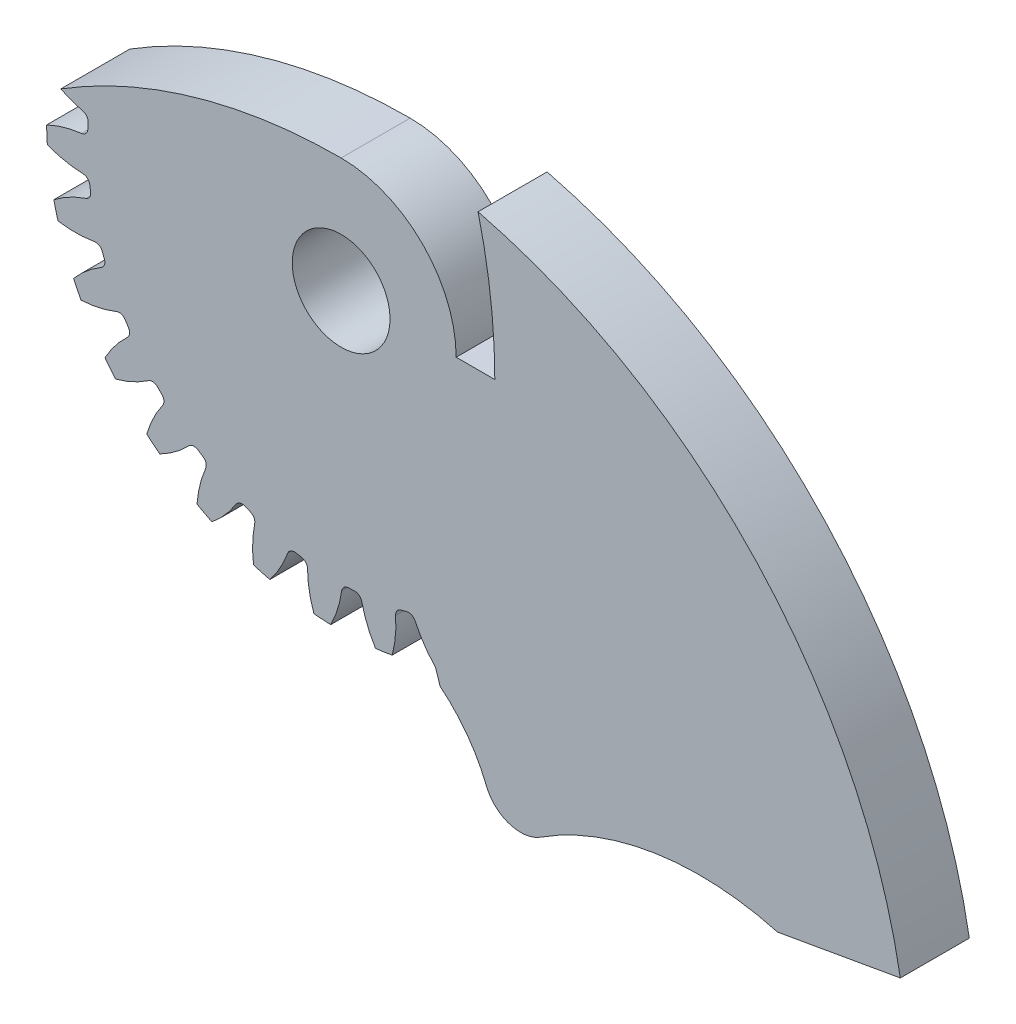
SolidWorks part; units mm, degrees
material "ABS"
ref_plane "Front" through (0, 0, 0) normal (0, 0, 1) x (1, 0, 0)
ref_plane "Top" through (0, 0, 0) normal (0, 1, 0) x (1, 0, 0)
ref_plane "Right" through (0, 0, 0) normal (1, 0, 0) x (0, 0, -1)
sketch "Sketch3" plane through (0, 0, 0) normal (0, 0, 1) x (1, 0, 0)
  circle A0 centre (0, 0) radius 40.64
  dimension "od" = 81.28
extrude "gearBody" add sketch "Sketch3" along normal blind 9.525
sketch "Sketch2" plane through (0, 0, 0) normal (0, 0, 1) x (1, 0, 0)
  line L0 (0, 0) -> (34.0786, 14.1158) construction
  line L1 (45.4751, -11.4855) -> (0, 0) construction
  line L2 (0, 0) -> (36.3143, 0) construction
  line L3 (38.0972, -0.458) -> (37.8451, -4.4001) construction
  line L5 (37.9712, -2.4291) -> (0, 0) construction
  line L7 (0, 0) -> (36.8864, 0) construction
  arc A0 (36.879, -0.7403) -> (36.6727, -3.9649) centre (0, 0) ccw construction
  arc A1 (40.637, 0.4947) -> (40.2427, -5.6687) centre (0, 0) ccw construction
  arc A2 (38.0972, -0.458) -> (37.8451, -4.4001) centre (0, 0) ccw construction
  arc A3 (34.9015, -2.6404) -> (34.9534, -1.8283) centre (0, 0) ccw
  arc A4 (45.4751, -11.4855) -> (35.6466, -3.6712) centre (32.0022, -18.3431) ccw
  arc A5 (45.4751, -11.4855) -> (46.5679, 5.5974) centre (0, 0) ccw
  arc A6 (46.5679, 5.5974) -> (35.8238, -0.9008) centre (34.0786, 14.1158) cw
  arc A7 (34.9534, -1.8283) -> (35.8238, -0.9008) centre (35.9376, -1.8798) cw
  arc A8 (35.6466, -3.6712) -> (34.9015, -2.6404) centre (35.8842, -2.7147) cw
  point P6 (46.5679, 5.5974)
  point P22 (45.4751, -11.4855)
  dimension "baseDia" = 73.7729
  dimension "od" = 81.28
  dimension "pd" = 76.2
  dimension "rd" = 70.0024
  dimension "rFillet" = 0.9855
  dimension "pointX" = 46.5679
  dimension "pointY" = 5.5974
  dimension "CTT" = 3.9421
  dimension "flankCenterAngle" = 22.5
extrude "toothCut" cut sketch "Sketch2" along normal through all
pattern_circular "CirPattern1" count 30 over 360 about axis through (0, 0, 9.525) along (0, 0, -1) of "toothCut"
sketch "hub1Dia" plane through (0, 0, 0) normal (0, 0, -1) x (-1, 0, 0)
  circle A0 centre (0, 0) radius 12.7
  dimension "hub1Dia" = 25.4
sketch "hub2Dia" plane through (0, 0, 9.525) normal (0, 0, 1) x (1, 0, 0)
  circle A0 centre (0, 0) radius 12.7
  dimension "hub2dia" = 25.4
sketch "boreDia" plane through (0, 0, 0) normal (0, 0, 1) x (1, 0, 0)
  circle A0 centre (0, 0) radius 6.7469
  dimension "boreDia" = 13.4937
extrude "bore" cut sketch "boreDia" against normal mid plane 25400
sketch "Sketch4" plane through (0, 0, 9.525) normal (0, 0, 1) x (1, 0, 0)
  circle A0 centre (0, -57.15) radius 78.359
  arc A2 (-42.9159, 8.4119) -> (42.9159, 8.4119) centre (0, 0) cw
  dimension "D1" = 156.718
  dimension "D2" = 57.15
extrude "Cut-Extrude1" cut sketch "Sketch4" against normal through all contours A0 region at (0, 27.8712, 9.525)
sketch "Sketch5" plane through (0, 0, 9.525) normal (0, 0, 1) x (1, 0, 0)
  line L0 (0, 21.209) -> (21.5163, 7.6712)
  line L1 (21.5163, 7.6712) -> (8.9608, -26.928)
  line L2 (8.9608, -26.928) -> (13.028, -38.4952)
  line L3 (0, 0) -> (0, -57.15) construction
  line L4 (0, -57.15) -> (-49.4328, 3.6491) construction
  line L5 (0, -57.15) -> (67.8609, -96.3295) construction
  line L6 (13.6543, -40.4261) -> (13.028, -38.4952)
  line L9 (0, -57.15) -> (77.1686, -43.5431) construction
  line L12 (60.232, -46.5295) -> (77.1686, -43.5431)
  circle A1 centre (0, -57.15) radius 78.359 construction
  arc A5 (0, 21.209) -> (77.1686, -43.5431) centre (0, -57.15) cw
  circle A6 centre (0, -57.15) radius 21.59 construction
  arc A10 (20.0525, -49.1485) -> (13.6543, -40.4261) centre (0, -57.15) ccw
  circle A12 centre (49.4934, -85.725) radius 40.64 construction
  arc A13 (27.5177, -51.539) -> (60.232, -46.5295) centre (49.4934, -85.725) cw
  arc A14 (27.5177, -51.539) -> (20.0525, -49.1485) centre (24.7708, -47.2658) cw
  point P28 (21.569, -56.1981)
  dimension "D1" = 43.18
  dimension "D3" = 81.28
  dimension "D7" = 5.08
  dimension "D6" = 156.718
  dimension "D2" = 120
  dimension "D4" = 57.15
  dimension "D5" = 80
extrude "Boss-Extrude1" add sketch "Sketch5" against normal up to surface (9.525 mm away) up to face at (6.7469, 0, 0)
sketch "Sketch6" plane through (0, 0, 9.525) normal (0, 0, 1) x (1, 0, 0)
  line L1 (-41.2829, 3.086) -> (-43.5386, 8)
  line L2 (15.875, 0) -> (21.209, 0)
  circle A0 centre (0, -57.15) radius 78.359 construction
  arc A1 (77.1686, -43.5431) -> (-36.286, 12.3011) centre (0, -57.15) ccw construction
  circle A2 centre (0, 0) radius 15.875 construction
  arc A3 (0, 15.875) -> (15.875, 0) centre (0, 0) cw
  arc A4 (18.8964, 18.8964) -> (-43.5386, 8) centre (0, -57.15) ccw
  arc A5 (0, 15.875) -> (-41.2829, 3.086) centre (0, -57.15) ccw
  circle A6 centre (0, 0) radius 21.209 construction
  circle A8 centre (-57.15, 0) radius 78.359 construction
  arc A9 (21.209, 0) -> (18.8964, 18.8964) centre (-57.15, 0) ccw
  dimension "D4" = 57.15
  dimension "D1" = 31.75
  dimension "D2" = 42.418
  dimension "D3" = 156.718
extrude "Cut-Extrude2" cut sketch "Sketch6" against normal through all
equation "\"Bodytube_OD\" = 6.17in"
equation "\"Bodytube_ID\" = 5.998in"
equation "\"Fwd_Tube_Length\" = 38in"
equation "\"Mid_Tube_Length\" = 8in"
equation "\"Aft_Section_Length\"= 40in"
equation "\"Mid_Coupler_Length\" = 13in"
equation "\"Aft_Lower_Length\"= 22in"
equation "\"AB_Coupler_OD_Length\"= 1in"
equation "\"AB_Coupling_Section_Length\"= 0.375in"
equation "\"AB_Coupler_Length\"= \"AB_Coupler_OD_Length\" + \"AB_Coupling_Section_Length\" * 2"
equation "\"Cutout_Angle\" = 80"
equation "\"AB_Paddle_Height\" = 0.375in"
equation "\"AB_Coupler_Num_Screws\"= 6"
equation "\"Num_Cutouts\" = 3"
equation "\"AB_Coupler_OD\"= 6.17in"
equation "\"AB_Coupler_ID\"= 5.75in"
equation "\"AB_Coupler_Surface_Diameter\"= 5.998in"
equation "\"AB_Coupling_Screw_Diameter\"= 0.1065in"
equation "\"AB_Central_Bushing_Length\" = .75in"
equation "\"Lead_Screw_Dist\" = 2.25in"
equation "\"Lead_Screw_Diam\" = (27/64)*1in"
equation "\"Lead_Screw_Length\" = (\"Mid_Coupler_Length\" + 2*0.375in + 2*0.5in)"
equation "\"Paddle_Pin_Offset\" = .25in"
equation "\"Paddle_Pin_Radius\" = 2.25in"
equation "\"Fwd_BKHD_From_Top\" = 18in"
equation "\"D1@Sketch4\"=\"Bodytube_OD\""
equation "\"D2@Sketch4\"=\"Paddle_Pin_Radius\""
equation "\"D3@Sketch5\"=\"Paddle_Gear_OD\""
equation "\"D4@Sketch5\"=\"Paddle_Pin_Radius\""
equation "\"Motor_OD\" = 4in"
equation "\"Aft_Upper_Length\"= \"Aft_Section_Length\" - \"Aft_Lower_Length\" - \"AB_Coupler_OD_Length\""
equation "\"Paddle_Gear_OD\" = 3.2in"
equation "\"D5@Sketch5\"=\"Cutout_Angle\""
equation "\"D6@Sketch5\"=\"Bodytube_OD\""
equation "\"D1@Sketch6\"=\"AB_Coupler_ID\"-2*\"Paddle_Pin_Radius\""
equation "\"D2@Sketch6\"=\"Bodytube_OD\"-2*\"Paddle_Pin_Radius\""
equation "\"D3@Sketch6\"=\"Bodytube_OD\""
equation "\"D4@Sketch6\"=\"Paddle_Pin_Radius\""
